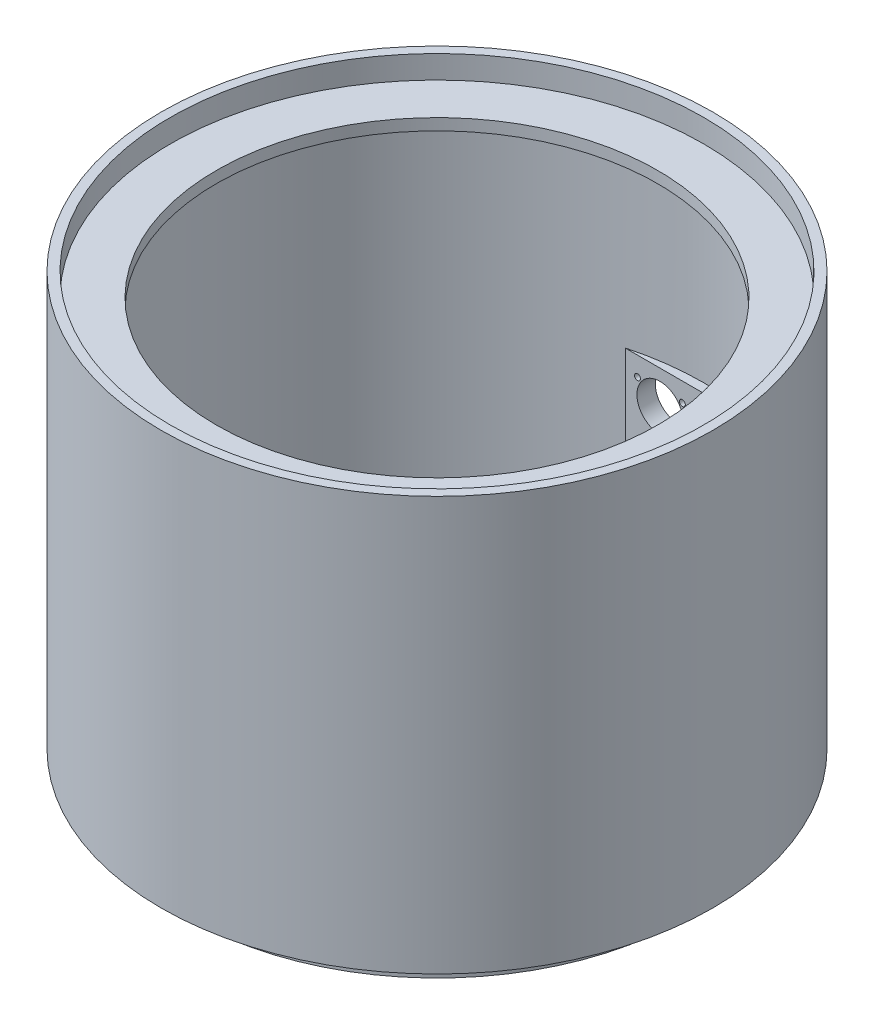
SolidWorks part; units mm, degrees
ref_plane "前基準面" through (0, 0, 0) normal (0, 0, 1) x (1, 0, 0)
ref_plane "上基準面" through (0, 0, 0) normal (0, 1, 0) x (1, 0, 0)
ref_plane "右基準面" through (0, 0, 0) normal (1, 0, 0) x (0, 0, -1)
sketch "草圖1" plane through (0, 0, 0) normal (1, 0, 0) x (0, 0, -1)
  line L0 (0, 0) -> (108, 0)
  line L1 (108, 0) -> (108, 10)
  line L2 (108, 10) -> (120, 10)
  line L3 (120, 10) -> (120, 190)
  line L4 (120, 190) -> (116, 190)
  line L5 (116, 190) -> (116, 180)
  line L6 (116, 180) -> (96, 180)
  line L7 (96, 180) -> (96, 175)
  line L8 (96, 175) -> (116, 175)
  line L9 (116, 175) -> (116, 15)
  line L10 (116, 15) -> (104, 15)
  line L11 (104, 15) -> (104, 5)
  line L12 (104, 5) -> (0, 5)
  line L13 (0, 5) -> (0, 0)
  point P12 (108, 5)
  point P16 (0, 2.5)
  point P17 (110, 15)
  dimension "D1" = 108
  dimension "D2" = 120
  dimension "D3" = 4
  dimension "D4" = 20
  dimension "D5" = 4
  dimension "D6" = 10
  dimension "D7" = 5
  dimension "D8" = 5
  dimension "D9" = 5
  dimension "D10" = 10
  dimension "D11" = 160
revolve "旋轉1" add sketch "草圖1" angle 360 about L13
sketch "草圖2" plane through (0, 0, 0) normal (0, -1, 0) x (1, 0, 0)
  line L0 (0, 0) -> (0, -108) construction
  line L1 (0, 0) -> (-120, 0) construction
  circle A0 centre (0, 0) radius 108 construction
  circle A1 centre (0, -15) radius 2.5
  circle A2 centre (0, 0) radius 120 construction
  circle A3 centre (0, -25) radius 2.5
  circle A4 centre (0, -35) radius 2.5
  circle A5 centre (0, -45) radius 2.5
  circle A6 centre (0, -55) radius 2.5
  circle A7 centre (0, -65) radius 2.5
  circle A8 centre (0, -75) radius 2.5
  circle A10 centre (0, -85) radius 2.5 [skipped]
  dimension "D1" = 5
  dimension "D2" = 15
  dimension "D4" = 25
  dimension "D3" = 8
extrude "除料-伸長1" cut sketch "草圖2" against normal up to next
ref_axis "基準軸1" through (0, 15, 0) along (0, 1, 0)
pattern_circular "環狀複製排列1" count 12 every 30 about axis through (0, 15, 0) along (0, 1, 0) of "除料-伸長1"
ref_plane "平面1" through (0, 0, -120) normal (0, 0, -1) x (-1, 0, 0)
sketch "草圖3" plane through (0, 0, -120) normal (0, 0, -1) x (-1, 0, 0)
  line L0 (0, 15) -> (0, 175) construction
  line L1 (-30, 45) -> (30, 45)
  line L2 (-30, 45) -> (-30, 90)
  line L3 (-30, 90) -> (30, 90)
  line L4 (30, 45) -> (30, 90)
  line L5 (-30, 45) -> (30, 90) construction
  line L6 (-30, 90) -> (30, 45) construction
  line L7 (120, 190) -> (-120, 190) construction
  point P0 (0, 67.5)
  dimension "D1" = 60
  dimension "D2" = 45
  dimension "D3" = 100
extrude "填料-伸長1" add sketch "草圖3" against normal blind 8
sketch "草圖4" plane through (0, 0, -120) normal (0, 0, -1) x (-1, 0, 0)
  line L0 (30, 45) -> (30, 90) construction
  line L1 (30, 90) -> (0, 90) construction
  line L2 (5.25, 81.7) -> (24.75, 81.7) construction
  line L3 (15, 75) -> (15, 81.7) construction
  line L4 (21, 83) -> (30, 83) construction
  line L5 (30, 90) -> (30, 45) construction
  line L6 (5.25, 83) -> (24.75, 83) construction
  line L7 (24.75, 81.7) -> (24.75, 47.7) construction
  line L8 (24.75, 47.7) -> (5.25, 47.7) construction
  line L9 (5.25, 47.7) -> (5.25, 81.7) construction
  circle A0 centre (15, 75) radius 10
  circle A1 centre (24.75, 81.7) radius 1.3
  circle A2 centre (5.25, 81.7) radius 1.3
  circle A3 centre (15, 75) radius 8 construction
  circle A4 centre (5.25, 47.7) radius 1.3
  circle A5 centre (24.75, 47.7) radius 1.3
  dimension "D1" = 20
  dimension "D2" = 15
  dimension "D4" = 19.5
  dimension "D5" = 16
  dimension "D6" = 2.6
  dimension "D7" = 34
  dimension "D3" = 15
extrude "除料-伸長2" cut sketch "草圖4" against normal up to next
sketch "草圖5" plane through (0, 0, -120) normal (0, 0, -1) x (-1, 0, 0)
  line L0 (-19, 87) -> (-19, 74) construction
  line L1 (-24.25, 64) -> (-13.75, 64) construction
  line L2 (-24.25, 64) -> (-24.25, 84) construction
  line L3 (-24.25, 84) -> (-13.75, 84) construction
  line L4 (-13.75, 64) -> (-13.75, 84) construction
  line L5 (-24.25, 64) -> (-13.75, 84) construction
  line L6 (-24.25, 84) -> (-13.75, 64) construction
  line L7 (-19, 74) -> (-19, 60.5) construction
  line L8 (0, 90) -> (-30, 90) construction
  line L9 (-25, 63) -> (-13, 63)
  line L10 (-25, 63) -> (-25, 85)
  line L11 (-25, 85) -> (-13, 85)
  line L12 (-13, 63) -> (-13, 85)
  line L13 (-25, 63) -> (-13, 85) construction
  line L14 (-25, 85) -> (-13, 63) construction
  line L15 (-30, 45) -> (-30, 90) construction
  circle A0 centre (-19, 87) radius 1.3
  circle A1 centre (-19, 60.5) radius 1.3
  point P0 (-19, 74)
  dimension "D3" = 3
  dimension "D4" = 26.5
  dimension "D5" = 2.6
  dimension "D1" = 10.5
  dimension "D2" = 20
  dimension "D6" = 22
  dimension "D7" = 12
  dimension "D8" = 5
  dimension "D9" = 5
extrude "除料-伸長3" cut sketch "草圖5" against normal up to next
